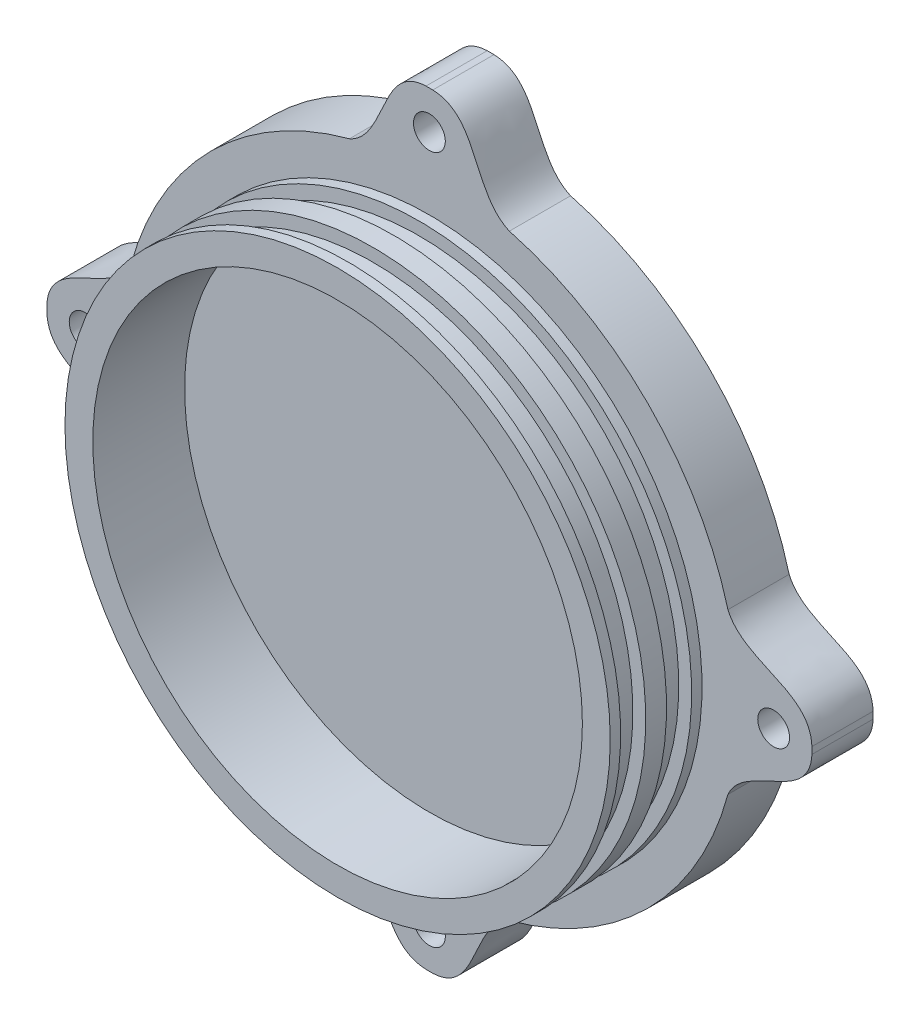
SolidWorks part; units mm, degrees
material "6063-T6"
ref_plane "Front Plane" through (0, 0, 0) normal (0, 0, 1) x (1, 0, 0)
ref_plane "Top Plane" through (0, 0, 0) normal (0, 1, 0) x (1, 0, 0)
ref_plane "Right Plane" through (0, 0, 0) normal (1, 0, 0) x (0, 0, -1)
sketch "Sketch1" plane through (0, 0, 0) normal (0, 0, 1) x (1, 0, 0)
  circle A0 centre (0, 0) radius 44.55
  dimension "D1" = 89.1
extrude "Boss-Extrude1" add sketch "Sketch1" along normal blind 15
sketch "Sketch2" plane through (0, 0, 0) normal (0, 0, -1) x (-1, 0, 0)
  circle A0 centre (0, 0) radius 62.5
  circle A1 centre (0, 0) radius 50 construction
  dimension "D1" = 125
  dimension "D2" = 100
extrude "Boss-Extrude2" add sketch "Sketch2" along normal blind 10
sketch "Sketch3" plane through (0, 0, 15) normal (0, 0, 1) x (1, 0, 0)
  circle A0 centre (0, 0) radius 40
  dimension "D1" = 80
extrude "Cut-Extrude1" cut sketch "Sketch3" against normal blind 15
sketch "Sketch4" plane through (0, 0, 0) normal (1, 0, 0) x (0, 0, -1)
  line L0 (42.7131, 0) -> (-42.7131, 0) construction
  line L1 (-48.1647, 44.55) -> (43.8613, 44.55) construction
  line L2 (-15, 44.55) -> (-15, -44.55) construction
  line L3 (0, 62.5) -> (0, -62.5) construction
  line L4 (-7.5, 59.1563) -> (-7.5, -7.7145) construction
  line L5 (-9.2, 44.55) -> (-13.3, 42.45) construction
  line L6 (-5.8, 42.45) -> (-1.7, 42.45)
  line L7 (-5.8, 42.45) -> (-5.8, 44.55)
  line L8 (-5.8, 44.55) -> (-1.7, 44.55)
  line L9 (-1.7, 42.45) -> (-1.7, 44.55)
  line L10 (-5.8, 42.45) -> (-1.7, 44.55) construction
  line L11 (-5.8, 44.55) -> (-1.7, 42.45) construction
  line L12 (-9.2, 42.45) -> (-13.3, 44.55) construction
  line L13 (-13.3, 42.45) -> (-13.3, 44.55)
  line L14 (-9.2, 44.55) -> (-13.3, 44.55)
  line L15 (-9.2, 42.45) -> (-9.2, 44.55)
  line L16 (-9.2, 42.45) -> (-13.3, 42.45)
  circle A0 centre (-3.75, 43.95) radius 1.5 construction
  circle A1 centre (-11.25, 43.95) radius 1.5 construction
  point P5 (0, 0)
  point P12 (-3.75, 43.5)
  point P23 (-11.25, 43.5)
  dimension "D5" = 1.5
  dimension "D1" = 44.55
  dimension "D2" = 15
  dimension "D3" = 7.5
  dimension "D4" = 3.75
revolve "Cut-Revolve1" cut sketch "Sketch4" angle 360 about L0
sketch "Sketch5" plane through (0, 0, 0) normal (0, 0, 1) x (1, 0, 0)
  circle A0 centre (0, 0) radius 44.75 construction
  circle A1 centre (0, 0) radius 50 construction
  circle A2 centre (0, 0) radius 45.975
  circle A3 centre (0, 0) radius 48.775
  dimension "D1" = 89.5
  dimension "D2" = 100
  dimension "D3" = 97.55
  dimension "D4" = 91.95
  dimension "D5" = 2.8
extrude "Cut-Extrude2" [suppressed] cut sketch "Sketch5" against normal blind 1.3
sketch "Sketch6" plane through (0, 0, -10) normal (0, 0, -1) x (-1, 0, 0)
  line L0 (-10.6066, -10.6066) -> (10.6066, 10.6066) construction
  circle A0 centre (-10.6066, -10.6066) radius 5.5
  circle A1 centre (10.6066, 10.6066) radius 5.1
  point P3 (0, 0)
  dimension "D1" = 11
  dimension "D2" = 30
  dimension "D3" = 10.2
extrude "Cut-Extrude3" [suppressed] cut sketch "Sketch6" against normal through all
sketch "Sketch7" plane through (0, 0, -10) normal (0, 0, -1) x (-1, 0, 0)
  line L0 (0, 0) -> (81.7368, 0) construction
  line L1 (50, -30.8838) -> (50, 30.8838) construction
  circle A0 centre (0, 0) radius 44.75 construction
  circle A1 centre (0, 0) radius 50 construction
  circle A3 centre (0, 0) radius 62.5 construction
  circle A4 centre (56.25, 0) radius 2.6
  circle A5 centre (56.25, 0) radius 5 construction
  point P12 (50, 0)
  dimension "D1" = 89.5
  dimension "D2" = 100
  dimension "D3" = 125
  dimension "D4" = 5.2
  dimension "D5" = 10
  dimension "D6" = 6.25
extrude "Cut-Extrude4" cut sketch "Sketch7" against normal through all
ref_axis "Axis1" through (0, 0, -45.8748) along (0, 0, 1)
pattern_circular "CirPattern1" count 4 over 360 about axis through (0, 0, -45.8748) along (0, 0, 1) of "Cut-Extrude4"
sketch "Sketch8" plane through (0, 0, 0) normal (0, 0, 1) x (1, 0, 0)
  line L0 (0, 0) -> (68.0582, 0) construction
  circle A0 centre (36.25, 0) radius 1.6
  circle A1 centre (0, 0) radius 36.25 construction
  dimension "D1" = 3.2
  dimension "D2" = 72.5
extrude "Cut-Extrude5" [suppressed] cut sketch "Sketch8" against normal blind 5
pattern_circular "CirPattern2" [suppressed] count 4 over 360 about axis through (0, 0, -45.8748) along (0, 0, 1) of bodies 129
sketch "Sketch10" plane through (0, 0, 0) normal (0, 0, 1) x (1, 0, 0)
  line L0 (0, 0) -> (66.0992, 0) construction
  line L1 (56.25, 0) -> (60.8462, 4.5962) construction
  line L2 (56.25, 0) -> (56.25, 7.5) construction
  line L3 (0, 0) -> (48.7793, 13.0704) construction
  circle A0 centre (0, 0) radius 50.5
  circle A1 centre (0, 0) radius 62.5
  spline S0 degree 3 poles (62.5, 0) (62.7289, 8.1554) (51.4602, 6.8897) (48.7793, 13.0704) knots 0 0 0 0 1 1 1 1
  spline S1 degree 3 poles (62.5, 0) (62.7289, -8.1554) (51.4602, -6.8897) (48.7793, -13.0704) knots 0 0 0 0 1 1 1 1
  spline S2 degree 3 poles (0, -62.5) (8.1554, -62.7289) (6.8897, -51.4602) (13.0704, -48.7793) knots 0 0 0 0 1 1 1 1
  spline S3 degree 3 poles (0, -62.5) (-8.1554, -62.7289) (-6.8897, -51.4602) (-13.0704, -48.7793) knots 0 0 0 0 1 1 1 1
  spline S4 degree 3 poles (-62.5, 0) (-62.7289, -8.1554) (-51.4602, -6.8897) (-48.7793, -13.0704) knots 0 0 0 0 1 1 1 1
  spline S5 degree 3 poles (-62.5, 0) (-62.7289, 8.1554) (-51.4602, 6.8897) (-48.7793, 13.0704) knots 0 0 0 0 1 1 1 1
  spline S6 degree 3 poles (0, 62.5) (-8.1554, 62.7289) (-6.8897, 51.4602) (-13.0704, 48.7793) knots 0 0 0 0 1 1 1 1
  spline S7 degree 3 poles (0, 62.5) (8.1554, 62.7289) (6.8897, 51.4602) (13.0704, 48.7793) knots 0 0 0 0 1 1 1 1
  point P41 (0, 0)
  dimension "D4" = 101
  dimension "D1" = 15
  dimension "D2" = 6.5
  dimension "D3" = 7.5
extrude "Cut-Extrude6" cut sketch "Sketch10" against normal blind 10 contours A1 S7 A0 S0 | S2 A1 S1 A0 | S4 A1 S3 A0 | S6 A1 S5 A0 region at (37.4256, 37.4256, 0) region at (37.4256, -37.4256, 0) region at (-37.4256, 37.4256, 0) region at (-37.4256, -37.4256, 0)
